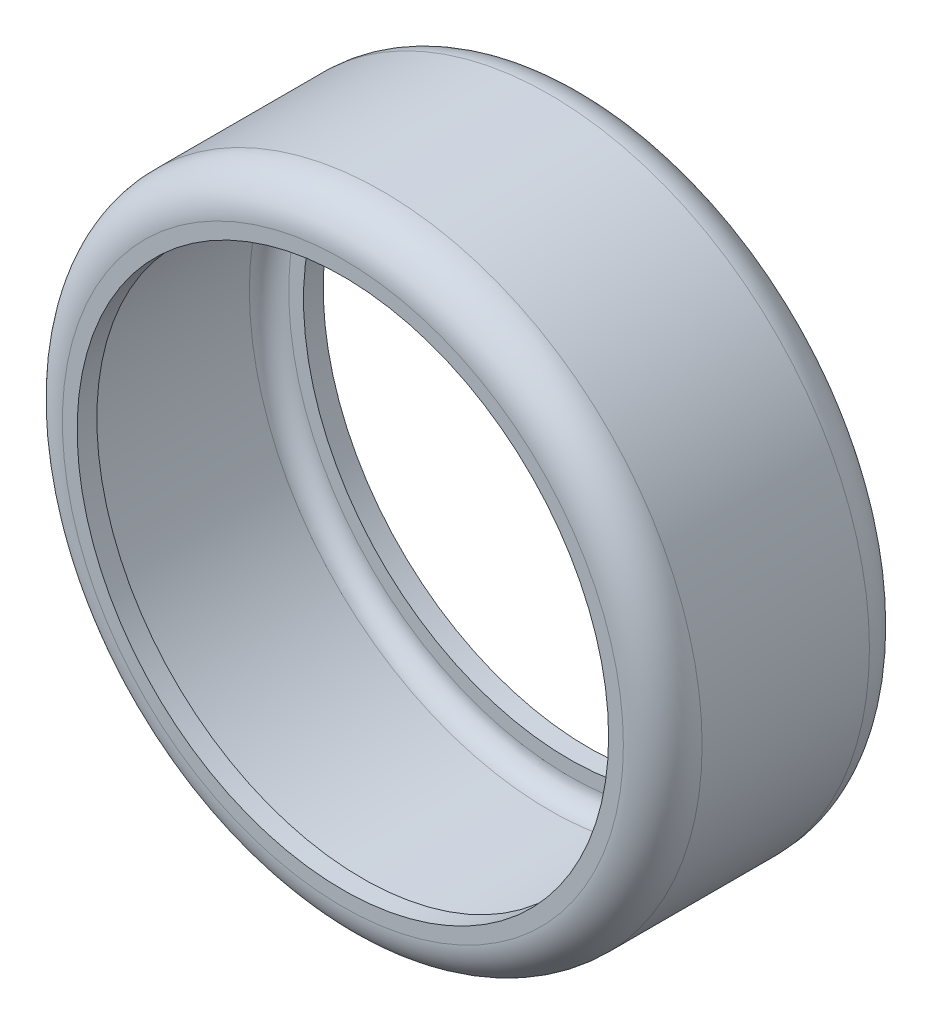
SolidWorks part; units mm, degrees
ref_plane "Спереди" through (0, 0, 0) normal (0, 0, 1) x (1, 0, 0)
ref_plane "Сверху" through (0, 0, 0) normal (0, 1, 0) x (1, 0, 0)
ref_plane "Справа" through (0, 0, 0) normal (1, 0, 0) x (0, 0, -1)
sketch "Эскиз1" plane through (0, 0, 0) normal (0, 0, 1) x (1, 0, 0)
  circle A0 centre (0, 0) radius 54
  dimension "D1" = 108
extrude "Вытянуть-Тонкостенный1" add sketch "Эскиз1" along normal blind 50 thin thin type one direction wall 11
fillet "Скругление1" radius 8 2 edges at (65, 0, 0) (65, 0, 50)
shell "Оболочка1" thickness 4 removed face at (54, 0, 50)
